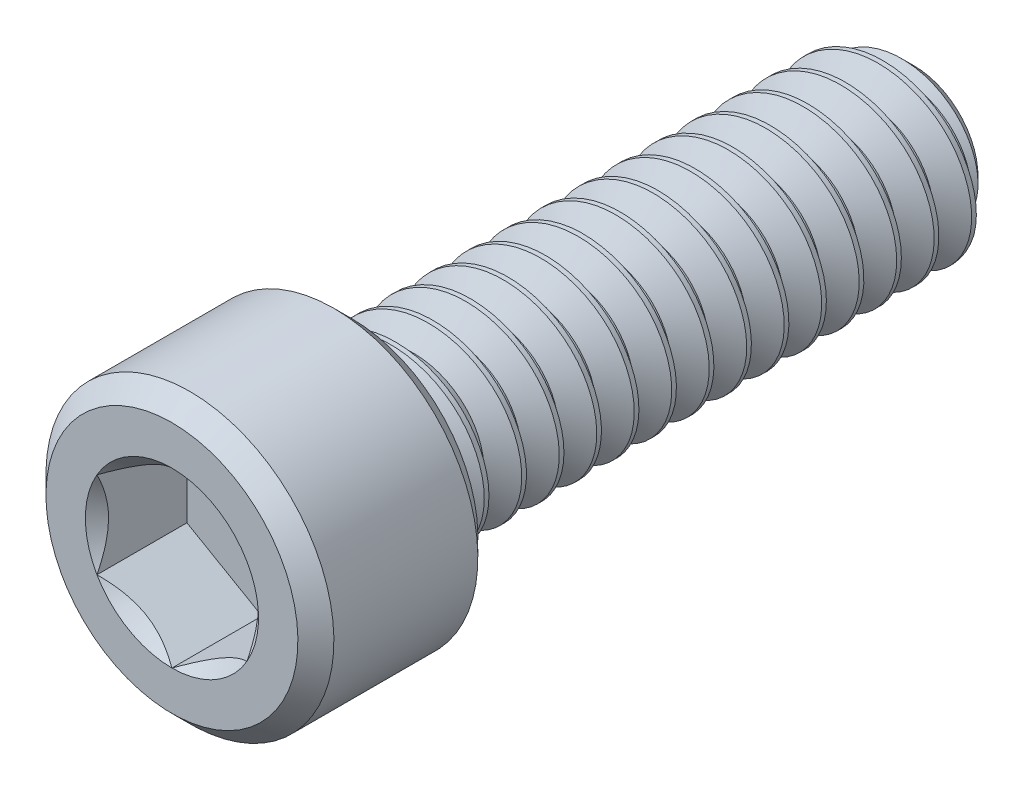
SolidWorks part; units mm, degrees
ref_plane "Front Plane" through (0, 0, 0) normal (0, 0, 1) x (1, 0, 0)
ref_plane "Top Plane" through (0, 0, 0) normal (0, 1, 0) x (1, 0, 0)
ref_plane "Right Plane" through (0, 0, 0) normal (1, 0, 0) x (0, 0, -1)
sketch "Sketch1" plane through (0, 0, 0) normal (1, 0, 0) x (0, 0, -1)
  line L0 (3.1433, 0) -> (-3.1433, 0) construction
  line L1 (-3.1433, 0) -> (-3.1433, 1.0668)
  line L2 (-3.1433, 1.0668) -> (-2.9909, 1.2192)
  line L3 (-2.9909, 1.2192) -> (-1.7717, 1.2192)
  line L4 (-1.7717, 1.2192) -> (-1.6193, 1.0668)
  line L5 (-1.6193, 1.0668) -> (-1.6192, 0.762)
  line L6 (-1.6192, 0.762) -> (2.921, 0.762)
  line L7 (2.921, 0.762) -> (3.1433, 0.5398)
  line L8 (3.1433, 0.5398) -> (3.1433, 0)
  line L9 (3.1234, 0.7964) -> (3.4409, 0.7964) construction
  line L10 (3.4409, 0.7964) -> (3.2822, 0.5214) construction
  line L11 (3.2822, 0.5214) -> (3.1234, 0.7964) construction
  line L12 (3.1433, 0.762) -> (3.4211, 0.762) construction
  line L13 (3.2822, 0.7964) -> (3.2822, 0.762) construction
  line L14 (3.2623, 0.5558) -> (3.302, 0.5558) construction
  line L15 (3.2822, 0.5558) -> (3.2822, 0.5214) construction
  line L16 (3.1333, 0.7792) -> (3.431, 0.7792)
  line L17 (3.431, 0.7792) -> (3.302, 0.5558)
  line L18 (3.302, 0.5558) -> (3.2623, 0.5558)
  line L19 (3.2623, 0.5558) -> (3.1333, 0.7792)
  line L20 (2.921, -0.762) -> (2.3495, -0.762) construction
  point P4 (0, 0)
  point P25 (3.2822, 0.7792)
  point P26 (3.1433, 0.762)
  point P33 (2.3495, -0.762)
  dimension "Head Ht" = 1.524
  dimension "Screw Size" = 1.524
  dimension "Head Dia" = 2.4384
  dimension "D1" = 45
  dimension "D2" = 45
  dimension "D3" = 0.1524
  dimension "D4" = 0.1524
  dimension "Pitch" = 0.3175
  dimension "D5" = 0.0397
  dimension "D6" = 0.2223
  dimension "D7" = 0.5715
  dimension "Length" = 4.7625
sketch "Sketch2" plane through (0, 0, 0) normal (0, 0, 1) x (1, 0, 0)
  line L1 (0, 0.7332) -> (-0.635, 0.3666)
  line L2 (-0.635, 0.3666) -> (-0.635, -0.3666)
  line L3 (-0.635, -0.3666) -> (0, -0.7332)
  line L4 (0, -0.7332) -> (0.635, -0.3666)
  line L5 (0.635, -0.3666) -> (0.635, 0.3666)
  line L6 (0.635, 0.3666) -> (0, 0.7332)
  circle A0 centre (0, 0) radius 0.635 construction
  circle A1 centre (0, 0) radius 1.2192
  point P1 (0, 1.2192)
  dimension "D1" = 2.4384
  dimension "Drive Size" = 1.27
sketch "Sketch3" plane through (0, 0, 0) normal (1, 0, 0) x (0, 0, -1)
  line L0 (3.1433, 0) -> (-3.1433, 0) construction
  line L1 (-3.1433, 0) -> (-3.1433, 1.0668) construction
  line L2 (-3.1433, 1.0668) -> (-2.9909, 1.2192) construction
  line L3 (-2.9909, 1.2192) -> (-1.7717, 1.2192) construction
  line L4 (-1.7717, 1.2192) -> (-1.6193, 1.0668) construction
  line L5 (-1.6193, 1.0668) -> (-1.6192, 0.762) construction
  line L6 (-1.6192, 0.762) -> (2.921, 0.762) construction
  line L7 (2.921, 0.762) -> (3.1433, 0.5398) construction
  line L8 (3.1433, 0.5398) -> (3.1433, 0) construction
  line L9 (3.1433, 0) -> (-3.1433, 0)
  line L10 (-3.1433, 0) -> (-3.1433, 1.0668)
  line L11 (-3.1433, 1.0668) -> (-2.9909, 1.2192)
  line L12 (-2.9909, 1.2192) -> (-1.7717, 1.2192)
  line L13 (-1.7717, 1.2192) -> (-1.6193, 1.0668)
  line L14 (-1.6193, 1.0668) -> (-1.6192, 0.762)
  line L15 (-1.6192, 0.762) -> (2.921, 0.762)
  line L16 (2.921, 0.762) -> (3.1433, 0.5398)
  line L17 (3.1433, 0.5398) -> (3.1433, 0)
revolve "Revolve1" add sketch "Sketch3" angle 360 about L0
sketch "Sketch4" plane through (0, 0, 3.1433) normal (0, 0, 1) x (1, 0, 0)
  line L0 (0, -0.7332) -> (0.635, -0.3666) construction
  line L1 (0.635, -0.3666) -> (0.635, 0.3666) construction
  line L2 (0.635, 0.3666) -> (0, 0.7332) construction
  line L3 (0, 0.7332) -> (-0.635, 0.3666) construction
  line L4 (-0.635, 0.3666) -> (-0.635, -0.3666) construction
  line L5 (-0.635, -0.3666) -> (0, -0.7332) construction
  line L6 (0, -0.7332) -> (0.635, -0.3666)
  line L7 (0.635, -0.3666) -> (0.635, 0.3666)
  line L8 (0.635, 0.3666) -> (0, 0.7332)
  line L9 (0, 0.7332) -> (-0.635, 0.3666)
  line L10 (-0.635, 0.3666) -> (-0.635, -0.3666)
  line L11 (-0.635, -0.3666) -> (0, -0.7332)
extrude "Cut-Extrude1" cut sketch "Sketch4" against normal blind 0.762
sketch "Sketch5" plane through (0, 0, 3.1433) normal (0, 0, 1) x (1, 0, 0)
  circle A0 centre (0, 0) radius 0.7332
extrude "Cut-Extrude3" cut sketch "Sketch5" against normal through all draft 45
split "Split1" bodies to split 107 resulting bodies 108 109 split by face at (0, 1.0668, 1.6193)
sketch "Sketch6" plane through (0, 0, -3.1433) normal (0, 0, -1) x (-1, 0, 0)
  circle A0 centre (0, 0) radius 0.762 construction
  circle A1 centre (0, 0) radius 0.762
curve "Helix/Spiral1" pitch 0.3175 height 5.08 radius 0.762 centre (0, 0, -3.1433) axis (0, 0, 1) start towards (0, 1, 0)
sketch "Sketch7" plane through (0, 0, 0) normal (1, 0, 0) x (0, 0, -1)
  line L0 (3.1333, 0.7792) -> (3.431, 0.7792) construction
  line L1 (3.431, 0.7792) -> (3.302, 0.5558) construction
  line L2 (3.302, 0.5558) -> (3.2623, 0.5558) construction
  line L3 (3.2623, 0.5558) -> (3.1333, 0.7792) construction
  line L4 (3.1333, 0.7792) -> (3.431, 0.7792)
  line L5 (3.431, 0.7792) -> (3.302, 0.5558)
  line L6 (3.302, 0.5558) -> (3.2623, 0.5558)
  line L7 (3.2623, 0.5558) -> (3.1333, 0.7792)
sweep "Cut-Sweep1" cut profiles "Sketch7" path "Helix/Spiral1" align with end faces yes
sketch "Sketch8" plane through (0, 0, 1.6193) normal (0, 0, -1) x (-1, 0, 0)
  circle A1 centre (0, 0) radius 0.762
extrude "Boss-Extrude1" add sketch "Sketch8" along normal up to next (4.7625 mm away) draft 20
equation "\"D3@Sketch1\"=\"Head Ht@Sketch1\"/10"
equation "\"D4@Sketch1\"=\"Head Ht@Sketch1\"/10"
equation "\"D5@Sketch1\"=\"Pitch@Sketch1\"/8"
equation "\"D6@Sketch1\"=\"Pitch@Sketch1\"*.7"
equation "\"D7@Sketch1\"=\"Pitch@Sketch1\"*2.5-\"D6@Sketch1\""
equation "\"D1@Cut-Extrude1\"=\"Head Ht@Sketch1\"/2"
equation "\"D4@Helix/Spiral1\"=\"Pitch@Sketch1\""
equation "\"D3@Helix/Spiral1\"=\"Length@Sketch1\"+\"D4@Helix/Spiral1\""
